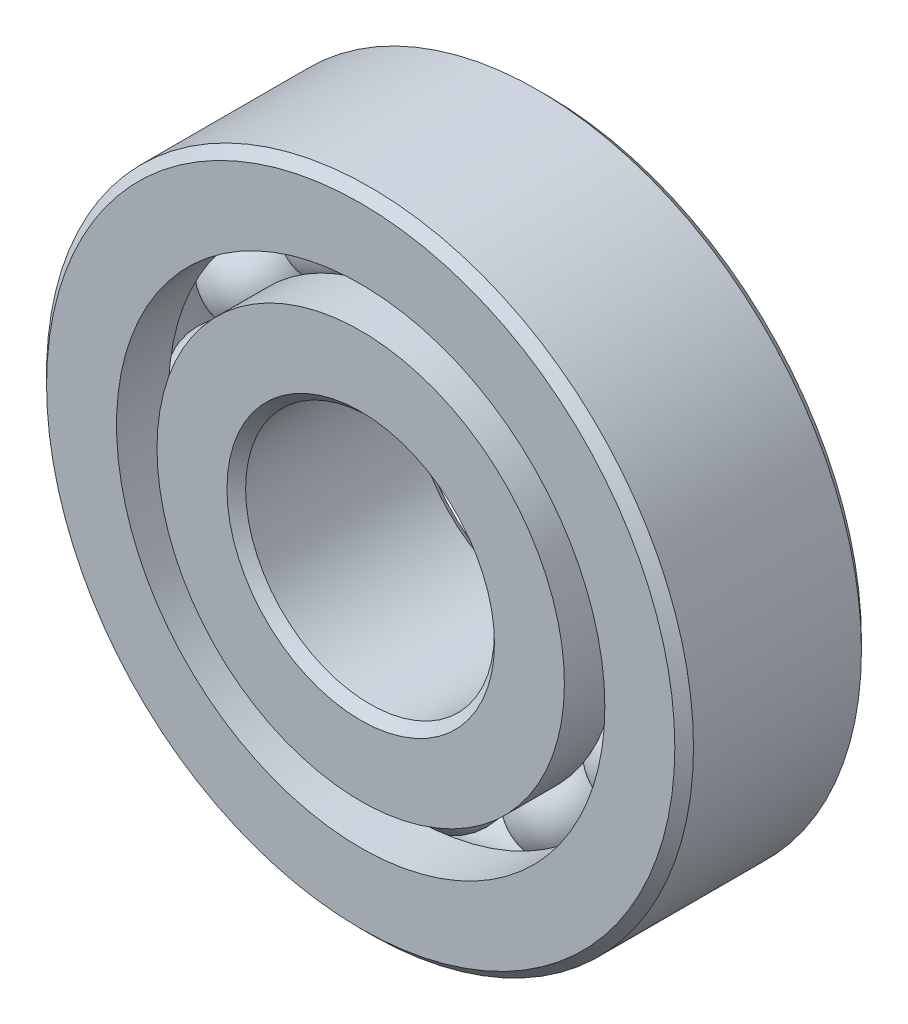
SolidWorks part; units mm, degrees
ref_plane "Front Plane" through (0, 0, 0) normal (0, 0, 1) x (1, 0, 0)
ref_plane "Top Plane" through (0, 0, 0) normal (0, 1, 0) x (1, 0, 0)
ref_plane "Right Plane" through (0, 0, 0) normal (1, 0, 0) x (0, 0, -1)
sketch "Sketch1" plane through (0, 0, 0) normal (1, 0, 0) x (0, 0, -1)
  line L0 (-7.5, 0) -> (7.5, 0) construction
  line L1 (0, 26) -> (0, -26) construction
  line L2 (6.75, 26) -> (-6.75, 26)
  line L3 (-6.75, 26) -> (-7.5, 25.25)
  line L4 (-7.5, 25.25) -> (-7.5, 19.6264)
  line L5 (-7.5, 19.6264) -> (-3.3333, 19.6264)
  line L6 (7.5, 19.6264) -> (3.3333, 19.6264)
  line L7 (7.5, 25.25) -> (7.5, 19.6264)
  line L8 (6.75, 26) -> (7.5, 25.25)
  line L9 (0, 26) -> (0, 18) construction
  line L10 (0, 18) -> (0, 10) construction
  arc A0 (-3.3333, 19.6264) -> (3.3333, 19.6264) centre (0, 18) cw
  point P14 (0, 10)
  dimension "Width" = 15
  dimension "OD" = 52
  dimension "D1" = 45
  dimension "D2" = 0.75
  dimension "Shaft Dia" = 20
  dimension "D3" = 6.6667
  dimension "D4" = 1.6264
revolve "Revolve1" add sketch "Sketch1" angle 360 about L0
sketch "Sketch3" plane through (0, 0, 0) normal (1, 0, 0) x (0, 0, -1)
  line L0 (-7.5, 16.3736) -> (-3.3333, 16.3736)
  line L1 (0, 26) -> (0, -26) construction
  line L2 (-7.5, 25.25) -> (-7.5, 19.6264) construction
  line L3 (-7.5, 16.3736) -> (-7.5, 10.75)
  line L4 (-6.75, 26) -> (-7.5, 25.25) construction
  line L5 (-7.5, 10.75) -> (-6.75, 10)
  line L6 (-6.75, 10) -> (6.75, 10)
  line L7 (6.75, 26) -> (6.75, -26) construction
  line L8 (6.75, 10) -> (7.5, 10.75)
  line L9 (7.5, -25.25) -> (7.5, 25.25) construction
  line L10 (7.5, 10.75) -> (7.5, 16.3736)
  line L11 (7.5, 16.3736) -> (3.3333, 16.3736)
  line L13 (6.75, 26) -> (7.5, 25.25) construction
  arc A0 (3.3333, 19.6264) -> (-3.3333, 19.6264) centre (0, 18) ccw construction
  arc A1 (3.3333, 16.3736) -> (-3.3333, 16.3736) centre (0, 18) cw
revolve "Revolve3" add sketch "Sketch3" angle 360 about L0
sketch "Sketch4" plane through (0, 0, 0) normal (1, 0, 0) x (0, 0, -1)
  line L0 (-3.7089, 18) -> (3.7089, 18)
  arc A2 (-3.7089, 18) -> (3.7089, 18) centre (0, 18) cw
  arc A3 (3.3333, 19.6264) -> (-3.3333, 19.6264) centre (0, 18) ccw construction
revolve "Revolve4" add sketch "Sketch4" angle 360 about L0
ref_axis "Axis1" through (0, 0, -7.5) along (0, 0, 1)
pattern_circular "CirPattern1" count 12 every 30 about axis through (0, 0, -7.5) along (0, 0, 1) of bodies 104
sketch "Sketch5" plane through (0, 0, 0) normal (1, 0, 0) x (0, 0, -1)
  line L0 (-7.5, 19.6264) -> (-3.3333, 19.6264) construction
  line L1 (-7.125, 19.6264) -> (-3.7089, 19.6264)
  line L2 (-7.125, 19.6264) -> (-7.125, 16.3736)
  line L3 (-7.125, 16.3736) -> (-3.7089, 16.3736)
  line L4 (-3.7089, 19.6264) -> (-3.7089, 16.3736)
  line L5 (-7.5, 16.3736) -> (-3.3333, 16.3736) construction
  line L6 (7.5, 19.6264) -> (3.3333, 19.6264) construction
  line L7 (7.125, 19.6264) -> (3.7089, 19.6264)
  line L8 (7.125, 19.6264) -> (7.125, 16.3736)
  line L9 (7.125, 16.3736) -> (3.7089, 16.3736)
  line L10 (3.7089, 19.6264) -> (3.7089, 16.3736)
  line L11 (7.5, 16.3736) -> (3.3333, 16.3736) construction
  line L12 (-6.75, 26) -> (-7.5, 25.25) construction
  point P18 (-7.125, 25.625)
equation "\"D2@Sketch1\" = \"Width@Sketch1\"*.05"
equation "\"D3@Sketch1\" = \"Width@Sketch1\"/2.25"
equation "\"D4@Sketch1\" = (((\"OD@Sketch1\"-\"Width@Sketch1\")/2)/3.25)/3.5"
equation "\"D2@CirPattern1\" = 360/\"Balls@CirPattern1\""
